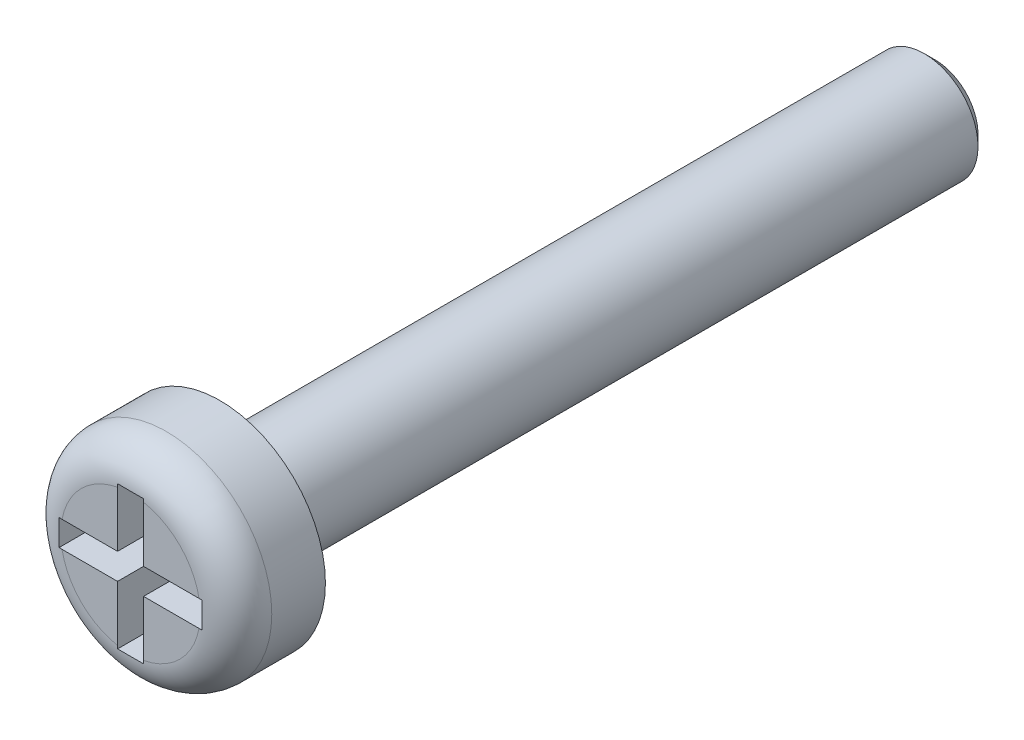
SolidWorks part; units mm, degrees
ref_plane "Front Plane" through (0, 0, 0) normal (0, 0, 1) x (1, 0, 0)
ref_plane "Top Plane" through (0, 0, 0) normal (0, 1, 0) x (1, 0, 0)
ref_plane "Right Plane" through (0, 0, 0) normal (1, 0, 0) x (0, 0, -1)
sketch "Sketch1" plane through (0, 0, 0) normal (0, 0, 1) x (1, 0, 0)
  circle A0 centre (0, 0) radius 2.95
  dimension "D1" = 5.9
extrude "Boss-Extrude1" add sketch "Sketch1" along normal blind 2.5
sketch "Sketch2" plane through (0, 0, 0) normal (0, 0, -1) x (-1, 0, 0)
  circle A0 centre (0, 0) radius 1.5
  dimension "D1" = 3
extrude "Boss-Extrude2" add sketch "Sketch2" along normal blind 20
chamfer "Chamfer1" distance 0.3 angle 45 1 edges at (-1.5, 0, -20)
sketch "Sketch3" plane through (0, 0, 2.5) normal (0, 0, 1) x (1, 0, 0)
  line L0 (0.3636, 0.3636) -> (2, 0.3636)
  line L1 (0.3636, -0.3636) -> (2, -0.3636)
  line L2 (-0.3636, 0.3636) -> (-0.3636, 2)
  line L3 (0.3636, 0.3636) -> (0.3636, 2)
  line L7 (-2, -0.3636) -> (-0.3636, -0.3636)
  line L8 (-2, -0.3636) -> (-2, 0.3636)
  line L9 (-2, 0.3636) -> (-0.3636, 0.3636)
  line L10 (2, -0.3636) -> (2, 0.3636)
  line L11 (-2, -0.3636) -> (2, 0.3636) construction
  line L12 (-2, 0.3636) -> (2, -0.3636) construction
  line L13 (-0.3636, -2) -> (0.3636, -2)
  line L14 (-0.3636, -2) -> (-0.3636, -0.3636)
  line L15 (-0.3636, 2) -> (0.3636, 2)
  line L16 (0.3636, -2) -> (0.3636, -0.3636)
  line L17 (-0.3636, -2) -> (0.3636, 2) construction
  line L18 (-0.3636, 2) -> (0.3636, -2) construction
  point P4 (0, 0)
  point P6 (0, 0)
  dimension "D1" = 4
extrude "Cut-Extrude1" cut sketch "Sketch3" against normal blind 2
fillet "Fillet1" radius 1 1 edges at (2.95, 0, 2.5)
